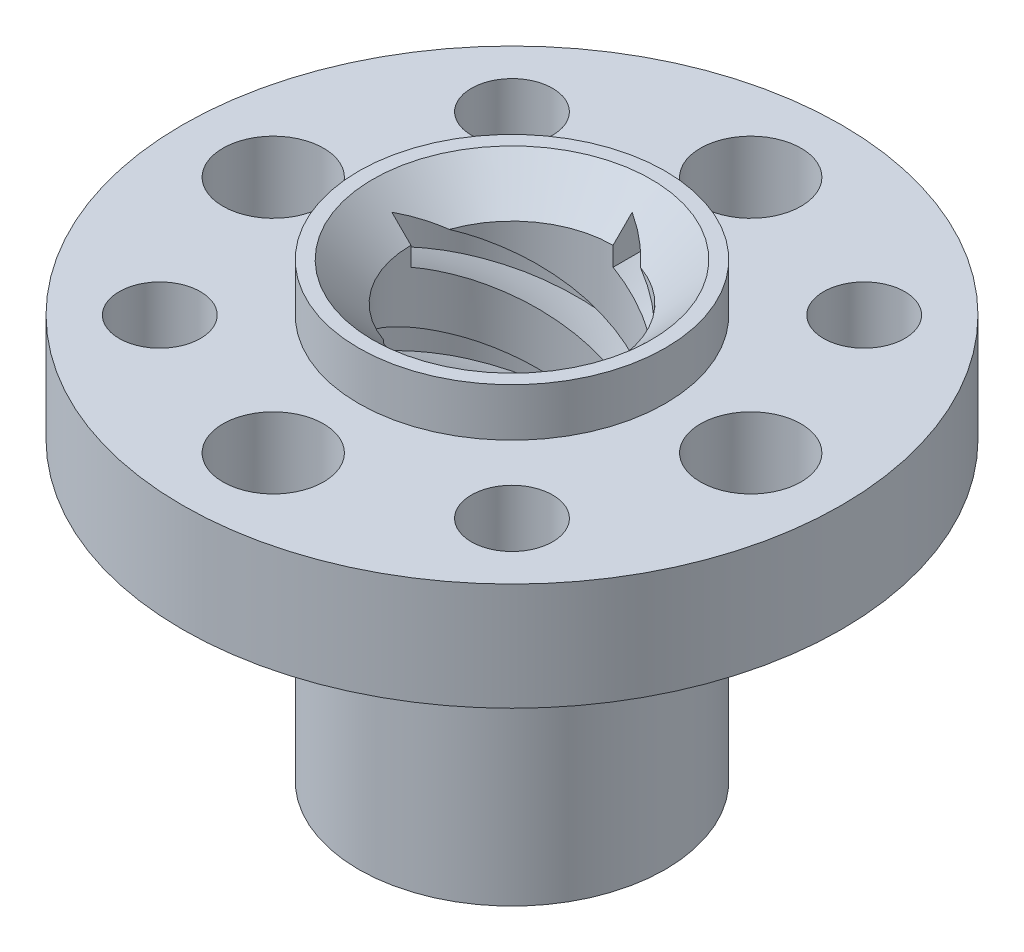
SolidWorks part; units mm, degrees
material "Brass"
ref_plane "Front Plane" through (0, 0, 0) normal (0, 0, 1) x (1, 0, 0)
ref_plane "Top Plane" through (0, 0, 0) normal (0, 1, 0) x (1, 0, 0)
ref_plane "Right Plane" through (0, 0, 0) normal (1, 0, 0) x (0, 0, -1)
sketch "Sketch1" plane through (0, 0, 0) normal (0, 0, 1) x (1, 0, 0)
  line L1 (3.3655, 15.0368) -> (5.1054, 15.0368)
  line L2 (5.1054, 15.0368) -> (5.1054, 13.4366)
  line L3 (5.1054, 13.4366) -> (10.9728, 13.4366)
  line L4 (10.9728, 13.4366) -> (10.9728, 9.8552)
  line L5 (10.9728, 9.8552) -> (5.1054, 9.8552)
  line L6 (5.1054, 9.8552) -> (5.1054, 0)
  line L8 (3.3655, 15.0368) -> (3.3655, 0)
  line L9 (3.3655, 0) -> (5.1054, 0)
  dimension "D1" = 3.3655
  dimension "D3" = 15.0368
  dimension "D4" = 1.6002
  dimension "D5" = 3.5814
  dimension "D6" = 10.9728
ref_axis "Centerline" through (0, 0, 0) along (0, 1, 0)
revolve "MainBod" add sketch "Sketch1" angle 360 about axis through (0, 0, 0) along (0, 1, 0)
sketch "Sketch2" plane through (0, 13.4366, 0) normal (0, 1, 0) x (1, 0, 0)
  circle A0 centre (7.9502, 0) radius 1.6764
  circle A1 centre (0, -7.9502) radius 1.6764
  circle A2 centre (-7.9502, 0) radius 1.6764
  circle A3 centre (0, 7.9502) radius 1.6764
  point P11 (0, 0)
  dimension "D3" = 3.3528
  dimension "D1" = 15.9004
  dimension "D2" = 4
extrude "Holes" cut sketch "Sketch2" against normal up to next
fillet "Shoulder" radius 0.254 1 edges at (0, 9.8552, -5.1054)
chamfer "Chamfer1" distance 1.27 angle 45 2 edges at (0, 0, -3.3655) (0, 15.0368, -3.3655)
sketch "Sketch3" plane through (0, 15.0368, 0) normal (0, 1, 0) x (1, 0, 0)
  circle A0 centre (0, 0) radius 3.3655 construction
  circle A1 centre (0, 0) radius 3.3655
curve "Helix/Spiral1" pitch 12 height 24 turns 2
sketch "Sketch4" plane through (0, 0, 0) normal (0, 0, 1) x (1, 0, 0)
  line L1 (-4.5085, 14.4018) -> (-2.2225, 14.4018)
  line L2 (-4.5085, 14.4018) -> (-4.5085, 13.1318)
  line L3 (-4.5085, 13.1318) -> (-2.2225, 13.1318)
  line L4 (-2.2225, 14.4018) -> (-2.2225, 13.1318)
  line L5 (-4.5085, 14.4018) -> (-2.2225, 13.1318) construction
  line L6 (-4.5085, 13.1318) -> (-2.2225, 14.4018) construction
  point P0 (-3.3655, 13.7668)
  dimension "D1" = 1.27
  dimension "D2" = 2.286
sweep "Cut-Sweep1" cut profiles "Sketch4" path "Helix/Spiral1"
pattern_circular "CirPattern1" count 4 over 360 about axis through (0, 15.0368, 0) along (0, -1, 0) of "Cut-Sweep1"
sketch "HolePattern" plane through (0, 13.4366, 0) normal (0, 1, 0) x (1, 0, 0)
  line L0 (10.9728, 0) -> (-10.9728, 0) construction
  line L1 (-3.6101, 3.6101) -> (-7.7589, 7.7589) construction
  circle A0 centre (0, 0) radius 5.1054 construction
  circle A1 centre (0, 0) radius 10.9728 construction
  point P0 (0, 0)
  point P9 (-5.8641, 5.8641)
  point P13 (5.8641, 5.8641)
  point P14 (5.8641, -5.8641)
  point P15 (-5.8641, -5.8641)
  point P16 (0, 0)
  point P21 (-5.6845, 5.6845)
  dimension "D1" = 45
  dimension "D3" = 0.254
  dimension "D2" = 4
hole_wizard "#6-32 Tapped Hole1" positions "Sketch8" profile "Sketch9" tap size "#6-32" standard "ANSI Inch" end condition through all
sketch "Sketch8" plane through (0, 13.4366, 0) normal (0, 1, 0) x (1, 0, 0)
  point P0 (-5.8641, 5.8641)
  point P3 (5.8641, 5.8641)
  point P6 (5.8641, -5.8641)
  point P9 (-5.8641, -5.8641)
sketch "Sketch9" plane through (-5.8641, 13.4366, -5.8641) normal (1, 0, 0) x (0, 0, 1)
  line L0 (0, 0) -> (0, 14.6644)
  line L1 (0, 14.6644) -> (1.3525, 14.6644)
  line L2 (1.3525, 14.6644) -> (1.3525, 0)
  line L5 (1.3525, 0) -> (0, 0)
  line L11 (0, -6.35) -> (0, 107.95) construction
  dimension "Thru Tap Drill Dia." = 2.7051
  dimension "Thru Tap Drill Depth" = 14.6644
cosmetic thread "Hole Thread1" parameters "D2"=3.5052
cosmetic thread "Hole Thread2" parameters "D2"=3.5052
cosmetic thread "Hole Thread3" parameters "D2"=3.5052
cosmetic thread "Hole Thread4" parameters "D2"=3.5052
equation "\"D6@Sketch1\"=0.864in/2"
equation "\"D1@Sketch1\"=0.265in/2"
equation "\"D2@Sketch1\"=0.402in/2"
equation "\"D1@Sketch2\"=0.494+\"D3@Sketch2\""
